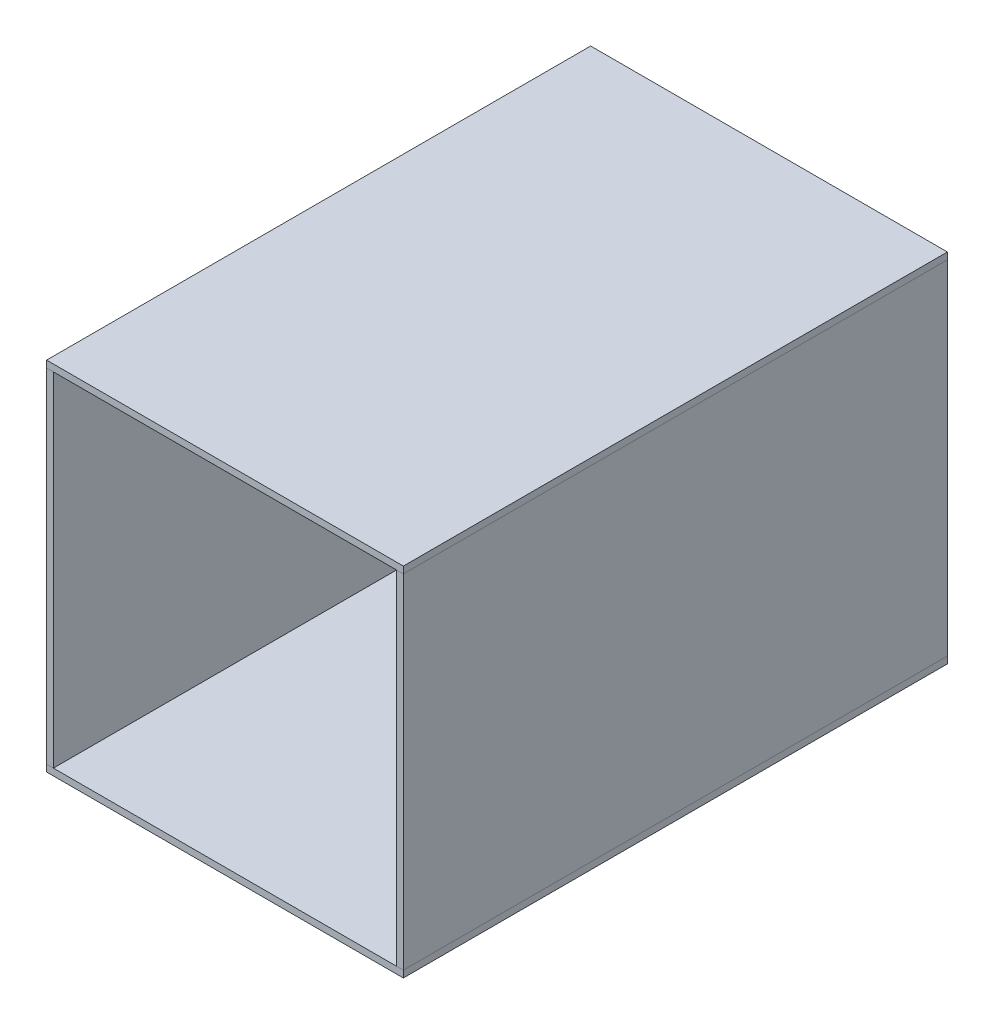
SolidWorks part; units mm, degrees
material "6061-T6 (SS)"
ref_plane "Front" through (0, 0, 0) normal (0, 0, 1) x (1, 0, 0)
ref_plane "Top" through (0, 0, 0) normal (0, 1, 0) x (1, 0, 0)
ref_plane "Right" through (0, 0, 0) normal (1, 0, 0) x (0, 0, -1)
sketch "Sketch1" plane through (0, 0, 0) normal (0, 0, 1) x (1, 0, 0)
  line L0 (-240.475, 9.525) -> (-240.475, 490.475)
  line L1 (-250, 0) -> (250, 0)
  line L2 (-250, 0) -> (-250, 500)
  line L3 (-250, 500) -> (250, 500)
  line L4 (250, 0) -> (250, 500)
  line L5 (-250, 490.475) -> (250, 490.475)
  line L6 (240.475, 9.525) -> (240.475, 490.475)
  line L7 (-250, 9.525) -> (250, 9.525)
  line L8 (-240.475, 490.475) -> (240.475, 490.475) construction
  line L9 (-240.475, 9.525) -> (240.475, 9.525) construction
  dimension "D1" = 500
  dimension "D2" = 9.525
extrude "Boss-Extrude1" add sketch "Sketch1" along normal blind 762.5 contours L2 L7 L0 L5 | L6 L7 L4 L5 region at (-245.2375, 250, 0) region at (245.2375, 250, 0)
extrude "Boss-Extrude2" add sketch "Sketch1<3>" along normal up to surface (762.5 mm away) separate body contours L2 L5 L4 L3 | L7 L2 L1 L4 region at (0, 4.7625, 0) region at (0, 495.2375, 0) up to face at (-245.2375, 250, 762.5)
sketch "Sketch1<3>" plane through (0, 0, 0) normal (0, 0, 1) x (1, 0, 0) same geometry as "Sketch1"
